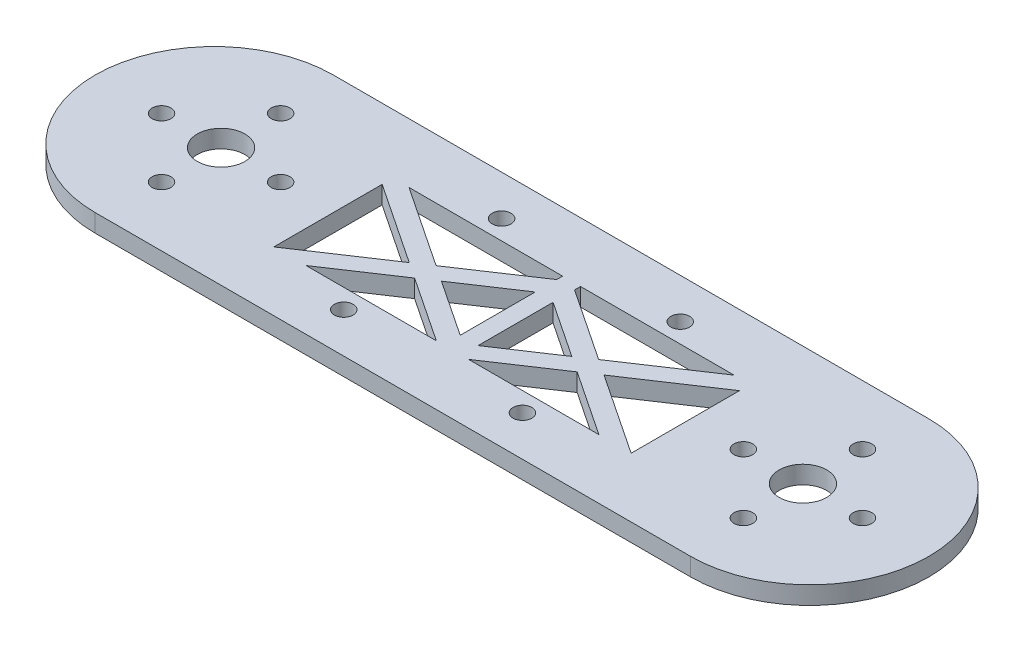
SolidWorks part; units mm, degrees
note: The reader was unsure of these and kept them because the rebuilt part matched: shared geometry of "Sketch1<3>".
ref_plane "Front Plane" through (0, 0, 0) normal (0, 0, 1) x (1, 0, 0)
ref_plane "Top Plane" through (0, 0, 0) normal (0, 1, 0) x (1, 0, 0)
ref_plane "Right Plane" through (0, 0, 0) normal (1, 0, 0) x (0, 0, -1)
sketch "Sketch1" plane through (0, 0, 0) normal (0, 1, 0) x (1, 0, 0)
  line L0 (-65, 0) -> (-62, 0)
  line L1 (-50, 20) -> (50, 20)
  line L2 (-50, 20) -> (-50, -20)
  line L3 (-50, -20) -> (50, -20)
  line L4 (50, 20) -> (50, -20)
  line L5 (-50, 20) -> (50, -20) construction
  line L6 (-50, -20) -> (50, 20) construction
  line L7 (-62, 0) -> (-59, 0)
  line L8 (-70, 0) -> (-65, 0)
  line L9 (-59, 0) -> (-48.85, 0)
  line L10 (-48.85, 10.15) -> (-48.85, 0)
  line L11 (-48.85, 13.15) -> (-48.85, 10.15)
  line L12 (-48.85, 16.15) -> (-48.85, 13.15)
  line L13 (-38.7, 0) -> (-48.85, 0)
  line L14 (-35.7, 0) -> (-38.7, 0)
  line L15 (-32.7, 0) -> (-35.7, 0)
  line L16 (-48.85, -10.15) -> (-48.85, 0)
  line L17 (-48.85, -13.15) -> (-48.85, -10.15)
  line L18 (-48.85, -16.15) -> (-48.85, -13.15)
  line L19 (0, 32.1937) -> (0, -35.5912)
  line L20 (48.85, -16.15) -> (48.85, -13.15)
  line L21 (70, 0) -> (65, 0)
  line L22 (65, 0) -> (62, 0)
  line L23 (62, 0) -> (59, 0)
  line L24 (48.85, -13.15) -> (48.85, -10.15)
  line L25 (48.85, -10.15) -> (48.85, 0)
  line L26 (48.85, 16.15) -> (48.85, 13.15)
  line L27 (48.85, 13.15) -> (48.85, 10.15)
  line L28 (48.85, 10.15) -> (48.85, 0)
  line L29 (59, 0) -> (48.85, 0)
  line L30 (32.7, 0) -> (35.7, 0)
  line L31 (35.7, 0) -> (38.7, 0)
  line L32 (38.7, 0) -> (48.85, 0)
  line L33 (0, 10) -> (-30, -10)
  line L34 (-30, 10) -> (30, 10)
  line L35 (-30, 10) -> (-30, -10)
  line L36 (-30, -10) -> (30, -10)
  line L37 (30, 10) -> (30, -10)
  line L38 (-30, 10) -> (30, -10) construction
  line L39 (-30, -10) -> (30, 10) construction
  line L40 (0, 10) -> (30, -10)
  line L41 (-1.5, 9) -> (-1.5, -10)
  line L42 (1.5, 9) -> (1.5, -10)
  line L43 (-24.5917, -10) -> (-1.5, 5.3944)
  line L44 (1.5, 5.3944) -> (24.5917, -10)
  line L45 (-30, 10) -> (-15, 0)
  line L46 (-30, 8.1972) -> (-16.3521, -0.9014)
  line L47 (-27.2958, 10) -> (-13.6479, 0.9014)
  line L48 (30, 8.1972) -> (16.3521, -0.9014)
  line L49 (27.2958, 10) -> (13.6479, 0.9014)
  line L50 (-1.5, 9) -> (-1.5, 10)
  line L51 (1.5, 9) -> (1.5, 10)
  line L52 (-13.6479, 0.9014) -> (-1.5, -7.1972)
  line L53 (-16.3521, -0.9014) -> (-2.7042, -10)
  line L54 (16.3521, -0.9014) -> (2.7042, -10)
  line L55 (13.6479, 0.9014) -> (1.5, -7.1972)
  line L56 (-15, 20) -> (-15, 13.25)
  arc A0 (-50, 20) -> (-50, -20) centre (-50, 0) ccw
  arc A1 (50, 20) -> (50, -20) centre (50, 0) cw
  circle A2 centre (-65, 0) radius 0.5
  circle A3 centre (-62, 0) radius 0.5
  circle A4 centre (-59, 0) radius 0.5
  circle A7 centre (-48.85, 10.15) radius 0.5
  circle A8 centre (-48.85, 13.15) radius 0.5
  circle A9 centre (-48.85, 16.15) radius 0.5
  circle A11 centre (-38.7, 0) radius 0.5
  circle A12 centre (-35.7, 0) radius 0.5
  circle A13 centre (-32.7, 0) radius 0.5
  circle A15 centre (-48.85, -10.15) radius 0.5
  circle A16 centre (-48.85, -13.15) radius 0.5
  circle A17 centre (-48.85, -16.15) radius 0.5
  circle A19 centre (-48.85, 0) radius 4
  circle A20 centre (48.85, -16.15) radius 0.5
  circle A21 centre (65, 0) radius 0.5
  circle A22 centre (62, 0) radius 0.5
  circle A23 centre (48.85, -13.15) radius 0.5
  circle A24 centre (48.85, -10.15) radius 0.5
  circle A25 centre (48.85, 16.15) radius 0.5
  circle A26 centre (48.85, 13.15) radius 0.5
  circle A27 centre (48.85, 10.15) radius 0.5
  circle A28 centre (32.7, 0) radius 0.5
  circle A29 centre (35.7, 0) radius 0.5
  circle A30 centre (38.7, 0) radius 0.5
  circle A31 centre (48.85, 0) radius 4
  circle A32 centre (-58.85, 0) radius 1.575
  circle A33 centre (-48.85, 10) radius 1.575
  circle A34 centre (-38.85, 0) radius 1.575
  circle A35 centre (-48.85, -10) radius 1.575
  circle A36 centre (58.85, 0) radius 1.575
  circle A37 centre (48.85, -10) radius 1.575
  circle A38 centre (38.85, 0) radius 1.575
  circle A39 centre (48.85, 10) radius 1.575
  circle A45 centre (-15, 13.25) radius 1.575
  circle A46 centre (15, 13.25) radius 1.575
  circle A47 centre (15, -13.25) radius 1.575
  circle A48 centre (-15, -13.25) radius 1.575
  point P0 (0, 0)
  point P45 (-48.85, 0)
  point P64 (0, 0)
  point P104 (-48.85, 0)
  point P113 (48.85, 0)
  dimension "D6" = 1
  dimension "D8" = 60
  dimension "D9" = 8
  dimension "D17" = 3.15
  dimension "D19" = 6.75
  dimension "D20" = 3.15
  dimension "D1" = 100
  dimension "D2" = 40
  dimension "D3" = 3
  dimension "D4" = 10.15
  dimension "D5" = 5
  dimension "D7" = 4
  dimension "D10" = 20
  dimension "D11" = 3
  dimension "D12" = 3
  dimension "D13" = 3
  dimension "D14" = 1.5
  dimension "D15" = 1.5
  dimension "D16" = 4
  dimension "D18" = 4
extrude "Boss-Extrude1" add sketch "Sketch1" along normal blind 3
extrude "Boss-Extrude2" add sketch "Sketch1<3>" along normal blind 3 contours L33 L41 L36 L19 | L42 L40 L19 L36 | L40 L51 L34 | L50 L33 L34
sketch "Sketch1<3>" plane through (0, 0, 0) normal (0, 1, 0) x (1, 0, 0) same geometry as "Sketch1"
